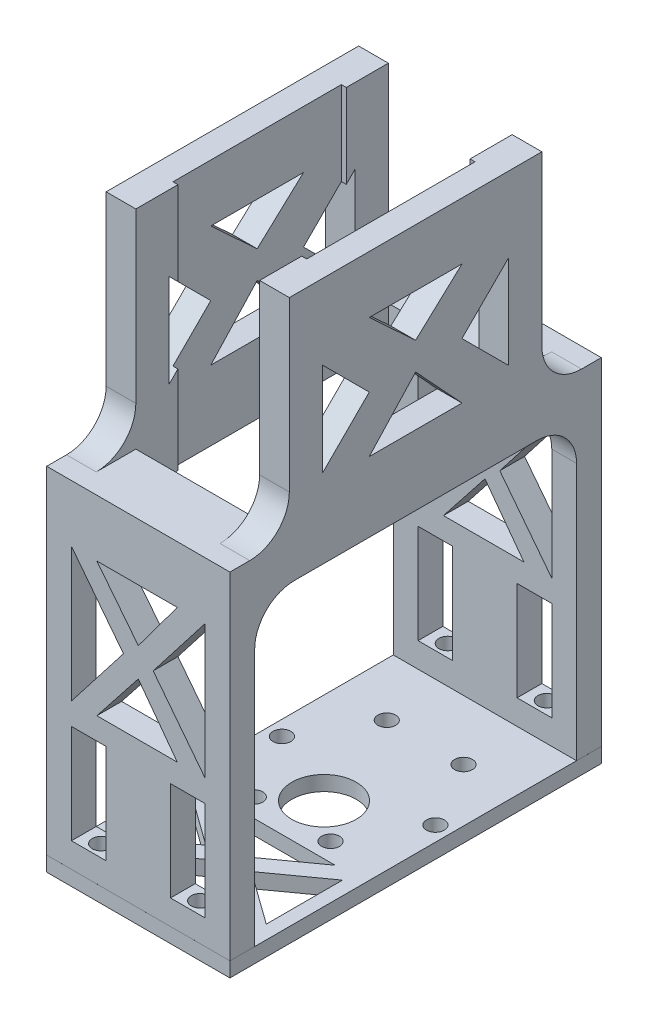
SolidWorks part; units mm, degrees
ref_plane "Front Plane" through (0, 0, 0) normal (0, 0, 1) x (1, 0, 0)
ref_plane "Top Plane" through (0, 0, 0) normal (0, 1, 0) x (1, 0, 0)
ref_plane "Right Plane" through (0, 0, 0) normal (1, 0, 0) x (0, 0, -1)
sketch "Sketch2" plane through (0, 0, 0) normal (0, 1, 0) x (1, 0, 0)
  line L1 (7.75, -13.4234) -> (15.5, 0) construction
  line L2 (15.5, 0) -> (7.75, 13.4234) construction
  line L3 (7.75, 13.4234) -> (-7.75, 13.4234) construction
  line L4 (-7.75, 13.4234) -> (-15.5, 0) construction
  line L5 (-15.5, 0) -> (-7.75, -13.4234) construction
  line L6 (-7.75, -13.4234) -> (7.75, -13.4234) construction
  circle A0 centre (0, 0) radius 13.4234 construction
  circle A1 centre (-15.5, 0) radius 1.8
  circle A2 centre (-7.75, 13.4234) radius 1.8
  circle A3 centre (7.75, 13.4234) radius 1.8
  circle A4 centre (15.5, 0) radius 1.8
  circle A5 centre (7.75, -13.4234) radius 1.8
  circle A6 centre (-7.75, -13.4234) radius 1.8
  circle A7 centre (0, 0) radius 18.5
  dimension "D2" = 3.6
  dimension "D3" = 37
  dimension "D1" = 31
extrude "Boss-Extrude1" add sketch "Sketch2" along normal blind 3
sketch "Sketch3" plane through (0, 3, 0) normal (0, 1, 0) x (1, 0, 0)
  line L0 (0, 0) -> (0, -7) construction
  circle A0 centre (0, -7) radius 6.5
  dimension "D2" = 13
  dimension "D1" = 7
extrude "Cut-Extrude1" cut sketch "Sketch3" against normal blind 3
sketch "Sketch4" plane through (0, 3, 0) normal (0, 1, 0) x (1, 0, 0)
  line L1 (-18.5, 30.5) -> (18.5, 30.5)
  line L4 (-18.5, -44.5) -> (18.5, -44.5)
  line L6 (-18.5, -44.5) -> (-18.5, 30.5)
  line L7 (18.5, 30.5) -> (18.5, -44.5)
  line L8 (0, -7) -> (2.9813, -7) construction
  circle A1 centre (0, 0) radius 18.5
  circle A2 centre (0, 0) radius 18.5
  point P7 (18.5, -7)
  circle M11 centre (0, 0) radius 18.5
  dimension "D2" = 75
  dimension "D1" = 0
extrude "Boss-Extrude2" add sketch "Sketch4" against normal up to surface (3 mm away) contours L7 L1 L6 M11 | L7 L6 L4 M11 region at (0, 3, -21.9811) region at (0, 3, 29.2305) up to face at (0, 0, 13.5)
sketch "Sketch5" plane through (0, 3, 0) normal (0, 1, 0) x (1, 0, 0)
  line L0 (18.5, 30.5) -> (18.5, -44.5) construction
  line L1 (-18.5, 30.5) -> (18.5, 30.5)
  line L2 (-18.5, 30.5) -> (-18.5, 25.5)
  line L3 (-18.5, 25.5) -> (18.5, 25.5)
  line L4 (18.5, 30.5) -> (18.5, 25.5)
  line L6 (-18.5, -44.5) -> (18.5, -44.5)
  line L7 (-18.5, -44.5) -> (-18.5, -39.5)
  line L8 (-18.5, -39.5) -> (18.5, -39.5)
  line L9 (18.5, -44.5) -> (18.5, -39.5)
  dimension "D1" = 5
extrude "Boss-Extrude3" add sketch "Sketch5" along normal blind 90
sketch "Sketch6" plane through (0, 93, 0) normal (0, 1, 0) x (1, 0, 0)
  line L0 (18.5, 25.5) -> (18.5, -39.5) construction
  line L1 (-18.5, 25.5) -> (18.5, 25.5)
  line L2 (-18.5, 25.5) -> (-18.5, 10)
  line L3 (-18.5, 10) -> (18.5, 10)
  line L4 (18.5, 25.5) -> (18.5, 10)
  line L6 (-18.5, -39.5) -> (18.5, -39.5)
  line L7 (-18.5, -39.5) -> (-18.5, -24)
  line L8 (-18.5, -24) -> (18.5, -24)
  line L9 (18.5, -39.5) -> (18.5, -24)
  dimension "D1" = 34
extrude "Boss-Extrude4" add sketch "Sketch6" against normal blind 5
sketch "Sketch7" plane through (0, 93, 0) normal (0, 1, 0) x (1, 0, 0)
  line L0 (18.5, 30.5) -> (-18.5, 30.5) construction
  line L1 (-18.5, 10) -> (-12.5, 10)
  line L2 (-18.5, 10) -> (-18.5, 30.5)
  line L3 (-18.5, 30.5) -> (-12.5, 30.5)
  line L4 (-12.5, 10) -> (-12.5, 30.5)
  line L5 (18.5, 10) -> (12.5, 10)
  line L6 (18.5, 10) -> (18.5, 30.5)
  line L7 (18.5, 30.5) -> (12.5, 30.5)
  line L8 (12.5, 10) -> (12.5, 30.5)
  line L9 (-18.5, -24) -> (-12.5, -24)
  line L10 (-18.5, -24) -> (-18.5, -44.5)
  line L11 (-18.5, -44.5) -> (-12.5, -44.5)
  line L12 (-12.5, -24) -> (-12.5, -44.5)
  line L13 (18.5, -24) -> (12.5, -24)
  line L14 (18.5, -24) -> (18.5, -44.5)
  line L15 (18.5, -44.5) -> (12.5, -44.5)
  line L16 (12.5, -24) -> (12.5, -44.5)
  dimension "D1" = 25
extrude "Boss-Extrude5" add sketch "Sketch7" along normal blind 20
sketch "Sketch8" plane through (0, 93, 0) normal (0, 1, 0) x (1, 0, 0)
  line L0 (-12.5, 10) -> (-12.5, 25.5)
  line L1 (-12.5, 10) -> (-12.5, 30.5) construction
  line L2 (-12.5, 25.5) -> (12.5, 25.5)
  line L3 (12.5, 30.5) -> (12.5, 10) construction
  line L4 (12.5, 25.5) -> (12.5, 10)
  line L5 (12.5, 10) -> (-12.5, 10)
  line L6 (-12.5, -24) -> (12.5, -24)
  line L7 (12.5, -24) -> (12.5, -39.5)
  line L8 (12.5, -24) -> (12.5, -44.5) construction
  line L9 (12.5, -39.5) -> (-12.5, -39.5)
  line L10 (-12.5, -44.5) -> (-12.5, -24) construction
  line L11 (-12.5, -39.5) -> (-12.5, -24)
  line L12 (-18.5, 25.5) -> (18.5, 25.5) construction
  line L13 (18.5, -39.5) -> (-18.5, -39.5) construction
extrude "Cut-Extrude2" cut sketch "Sketch8" against normal blind 10
sketch "Sketch9" plane through (0, 93, 0) normal (0, 1, 0) x (1, 0, 0)
  line L0 (12.5, 30.5) -> (12.5, 10) construction
  line L1 (-12.5, 30.5) -> (12.5, 30.5)
  line L2 (-12.5, 30.5) -> (-12.5, 25.5)
  line L3 (-12.5, 25.5) -> (12.5, 25.5)
  line L4 (12.5, 30.5) -> (12.5, 25.5)
  line L5 (-18.5, 25.5) -> (18.5, 25.5) construction
  line L7 (-12.5, -39.5) -> (12.5, -39.5)
  line L8 (-12.5, -39.5) -> (-12.5, -44.5)
  line L9 (-12.5, -44.5) -> (12.5, -44.5)
  line L10 (12.5, -39.5) -> (12.5, -44.5)
extrude "Boss-Extrude6" add sketch "Sketch9" along normal up to surface (20 mm away) up to face at (-15.5, 113, -20.25)
sketch "Sketch10" plane through (0, 0, 24) normal (0, 0, -1) x (-1, 0, 0)
  line L0 (12.5, 88) -> (18.5, 88) construction
  line L1 (18.5, 113) -> (13.5, 113)
  line L2 (18.5, 113) -> (18.5, 88)
  line L3 (18.5, 88) -> (13.5, 88)
  line L4 (13.5, 113) -> (13.5, 88)
  line L5 (-18.5, 88) -> (-12.5, 88) construction
  line L6 (-18.5, 113) -> (-13.5, 113)
  line L7 (-18.5, 113) -> (-18.5, 88)
  line L8 (-18.5, 88) -> (-13.5, 88)
  line L9 (-13.5, 113) -> (-13.5, 88)
  dimension "D1" = 5
extrude "Boss-Extrude7" add sketch "Sketch10" along normal up to next
sketch "Sketch11" plane through (0, 0, 44.5) normal (0, 0, 1) x (1, 0, 0)
  line L0 (-18.5, 113) -> (18.5, 113) construction
  line L1 (-12.5, 113) -> (12.5, 113)
  line L2 (-12.5, 113) -> (-12.5, 93)
  line L3 (-12.5, 93) -> (12.5, 93)
  line L4 (12.5, 113) -> (12.5, 93)
  line L7 (0, 93) -> (0, 113) construction
  line L8 (-18.5, 0) -> (-18.5, 113) construction
  line L9 (18.5, 0) -> (18.5, 113) construction
  line L10 (-12.5, 113) -> (-12.5, 88) construction
  dimension "D1" = 20
extrude "Cut-Extrude3" cut sketch "Sketch11" against normal through all
ref_plane "Plane1" through (12.5, 88, 39.5) normal (1, 0, 0) x (0, 0, -1)
sketch "Sketch13" plane through (18.5, 0, 0) normal (1, 0, 0) x (0, 0, -1)
  line L1 (-44.5, 113) -> (-32.5, 113)
  line L2 (-44.5, 113) -> (-44.5, 63)
  line L3 (-44.5, 63) -> (-32.5, 63)
  line L4 (-32.5, 113) -> (-32.5, 63)
  line L5 (30.5, 113) -> (18.5, 113)
  line L6 (30.5, 113) -> (30.5, 63)
  line L7 (30.5, 63) -> (18.5, 63)
  line L8 (18.5, 113) -> (18.5, 63)
  dimension "D1" = 12
  dimension "D2" = 50
extrude "Cut-Extrude5" cut sketch "Sketch13" against normal through all
sketch "Sketch14" plane through (0, 88, 0) normal (0, -1, 0) x (1, 0, 0)
  line L8 (18.5, -18.5) -> (18.5, 32.5)
  line L9 (18.5, 32.5) -> (12.5, 32.5)
  line L10 (12.5, 32.5) -> (12.5, 24)
  line L11 (12.5, 24) -> (13.5, 24)
  line L12 (13.5, 24) -> (13.5, -10)
  line L13 (13.5, -10) -> (12.5, -10)
  line L14 (12.5, -10) -> (12.5, -18.5)
  line L15 (12.5, -18.5) -> (18.5, -18.5)
  line L16 (18.5, -18.5) -> (18.5, 32.5)
  line L17 (18.5, 32.5) -> (12.5, 32.5)
  line L18 (12.5, 32.5) -> (12.5, 24)
  line L19 (12.5, 24) -> (13.5, 24)
  line L20 (13.5, 24) -> (13.5, -10)
  line L21 (13.5, -10) -> (12.5, -10)
  line L22 (12.5, -10) -> (12.5, -18.5)
  line L23 (12.5, -18.5) -> (18.5, -18.5)
  line L24 (-12.5, 32.5) -> (-18.5, 32.5)
  line L25 (-18.5, 32.5) -> (-18.5, -18.5)
  line L26 (-18.5, -18.5) -> (-12.5, -18.5)
  line L27 (-12.5, -18.5) -> (-12.5, -10)
  line L28 (-12.5, -10) -> (-13.5, -10)
  line L29 (-13.5, -10) -> (-13.5, 24)
  line L30 (-13.5, 24) -> (-12.5, 24)
  line L31 (-12.5, 24) -> (-12.5, 32.5)
  line L32 (-12.5, 32.5) -> (-18.5, 32.5)
  line L33 (-18.5, 32.5) -> (-18.5, -18.5)
  line L34 (-18.5, -18.5) -> (-12.5, -18.5)
  line L35 (-12.5, -18.5) -> (-12.5, -10)
  line L36 (-12.5, -10) -> (-13.5, -10)
  line L37 (-13.5, -10) -> (-13.5, 24)
  line L38 (-13.5, 24) -> (-12.5, 24)
  line L39 (-12.5, 24) -> (-12.5, 32.5)
  dimension "D1" = 0
  dimension "D2" = 0
extrude "Boss-Extrude8" add sketch "Sketch14" along normal up to surface (25 mm away) up to face at (0, 63, 42)
sketch "Sketch16" plane through (0, 0, 32.5) normal (0, 0, 1) x (1, 0, 0)
  line L0 (18.5, 63) -> (18.5, 113) construction
  line L1 (-18.5, 63) -> (18.5, 63)
  line L2 (-18.5, 63) -> (-18.5, 71)
  line L3 (-18.5, 71) -> (18.5, 71)
  line L4 (18.5, 63) -> (18.5, 71)
  line L5 (-18.5, 63) -> (-18.5, 113) construction
  dimension "D1" = 8
extrude "Boss-Extrude9" add sketch "Sketch16" along normal up to surface (12 mm away) up to face at (0, 31.5, 44.5)
sketch "Sketch17" plane through (0, 0, -18.5) normal (0, 0, -1) x (-1, 0, 0)
  line L0 (-18.5, 71) -> (18.5, 71) construction
  line L1 (-18.5, 71) -> (18.5, 71)
  line L2 (18.5, 63) -> (-18.5, 63) construction
  line L3 (18.5, 63) -> (-18.5, 63)
  line L4 (-18.5, 63) -> (-18.5, 71)
  line L5 (18.5, 63) -> (18.5, 71)
extrude "Boss-Extrude10" add sketch "Sketch17" along normal up to surface (12 mm away) up to face at (0, 31.5, -30.5)
fillet "Fillet1" radius 8 2 edges at (0, 63, -25.5) (0, 63, 39.5)
fillet "Fillet2" radius 8 4 edges at (15.5, 71, -18.5) (-15.5, 71, -18.5) (-15.5, 71, 32.5) (15.5, 71, 32.5)
sketch "Sketch18" plane through (0, 3, 0) normal (0, 1, 0) x (1, 0, 0)
  line L4 (18.5, -44.5) -> (18.5, 30.5)
  line L5 (-18.5, -44.5) -> (18.5, -44.5)
  line L6 (-18.5, 30.5) -> (-18.5, -44.5)
  line L7 (18.5, 30.5) -> (-18.5, 30.5)
  line L8 (18.5, -44.5) -> (18.5, 30.5)
  line L9 (-18.5, -44.5) -> (18.5, -44.5)
  line L10 (-18.5, 30.5) -> (-18.5, -44.5)
  line L11 (18.5, 30.5) -> (-18.5, 30.5)
  dimension "D1" = 0
extrude "Cut-Extrude6" cut sketch "Sketch18" along normal blind 0.001
sketch "Sketch19" plane through (0, 0, 0) normal (0, -1, 0) x (1, 0, 0)
  line L0 (-18.5, -30.5) -> (-18.5, -25.5) construction
  line L1 (-18.5, -30.5) -> (-18.5, -25.5) construction
  line L2 (-18.5, 39.5) -> (-18.5, 44.5) construction
  line L3 (-18.5, 39.5) -> (-18.5, 44.5) construction
  line L4 (18.5, 44.5) -> (18.5, 39.5) construction
  line L5 (18.5, 44.5) -> (18.5, 39.5) construction
  line L6 (18.5, -25.5) -> (18.5, -30.5) construction
  line L7 (18.5, -25.5) -> (18.5, -30.5) construction
  line L8 (-18.5, 42) -> (18.5, 42) construction
  line L9 (-18.5, -28) -> (18.5, -28) construction
  line L10 (0, 0) -> (0, -6.5767) construction
  circle A0 centre (-10, 42) radius 1.8
  circle A1 centre (10, 42) radius 1.8
  circle A2 centre (-10, -28) radius 1.8
  circle A3 centre (10, -28) radius 1.8
  dimension "D1" = 3.6
  dimension "D2" = 10
  dimension "D3" = 10
extrude "Cut-Extrude7" cut sketch "Sketch19" against normal blind 8
sketch "Sketch20" plane through (0, 8, 0) normal (0, -1, 0) x (1, 0, 0)
  line L0 (18.5, 44.5) -> (-18.5, 44.5) construction
  line L1 (-13.5, 44.5) -> (-6.5, 44.5)
  line L2 (-13.5, 44.5) -> (-13.5, 39.5)
  line L3 (-13.5, 39.5) -> (-6.5, 39.5)
  line L4 (-6.5, 44.5) -> (-6.5, 39.5)
  line L5 (-13.5, 44.5) -> (-6.5, 39.5) construction
  line L6 (-13.5, 39.5) -> (-6.5, 44.5) construction
  line L7 (6.5, 44.5) -> (13.5, 44.5)
  line L8 (6.5, 44.5) -> (6.5, 39.5)
  line L9 (6.5, 39.5) -> (13.5, 39.5)
  line L10 (13.5, 44.5) -> (13.5, 39.5)
  line L11 (6.5, 44.5) -> (13.5, 39.5) construction
  line L12 (6.5, 39.5) -> (13.5, 44.5) construction
  line L13 (0, 7) -> (3.3966, 7) construction
  line L14 (-13.5, -30.5) -> (-13.5, -25.5)
  line L15 (-13.5, -30.5) -> (-6.5, -30.5)
  line L16 (-6.5, -30.5) -> (-6.5, -25.5)
  line L17 (6.5, -25.5) -> (13.5, -25.5)
  line L18 (-13.5, -25.5) -> (-6.5, -25.5)
  line L19 (13.5, -30.5) -> (13.5, -25.5)
  line L20 (6.5, -30.5) -> (13.5, -30.5)
  line L21 (6.5, -30.5) -> (6.5, -25.5)
  point P0 (-10, 42)
  point P6 (10, 42)
  dimension "D1" = 7
extrude "Cut-Extrude8" cut sketch "Sketch20" against normal blind 20
sketch "Sketch21" plane through (-18.5, 0, 0) normal (-1, 0, 0) x (0, 0, 1)
  line L0 (-18.5, 113) -> (18.536, 78.964) construction
  line L4 (32.5, 113) -> (-0.1808, 77.4386) construction
  line L5 (-11.8064, 97.8512) -> (-11.8064, 78.964)
  line L7 (-11.8064, 78.964) -> (-2.3628, 88.4076)
  line L8 (-2.3628, 88.4076) -> (-11.8064, 97.8512)
  line L9 (7, 3) -> (7, 20.8388) construction
  line L10 (44.5, 3) -> (-30.5, 3) construction
  line L11 (25.8064, 78.964) -> (16.3628, 88.4076)
  line L12 (25.8064, 97.8512) -> (25.8064, 78.964)
  line L13 (16.3628, 88.4076) -> (25.8064, 97.8512)
  line L14 (-2.3628, 77.1233) -> (16.3628, 77.1233)
  line L15 (16.3628, 77.1233) -> (7, 87.2415)
  line L16 (7, 87.2415) -> (-2.3628, 77.1233)
  line L17 (-2.3628, 101.4479) -> (16.3628, 101.4479)
  line L18 (16.3628, 101.4479) -> (7, 92.7841)
  line L19 (7, 92.7841) -> (-2.3628, 101.4479)
extrude "Cut-Extrude9" cut sketch "Sketch21" against normal through all and the other way through all
sketch "Sketch22" plane through (0, 0, -30.5) normal (0, 0, -1) x (-1, 0, 0)
  line L0 (0, 71) -> (0, 24.1527) construction
  line L1 (18.5, 71) -> (-18.5, 71) construction
  line L2 (-13.5, 28) -> (-13.5, 59.5) construction
  line L3 (-13.5, 59.5) -> (-3, 45.9688)
  line L4 (-3, 45.9688) -> (-13.5, 32.4375)
  line L5 (-13.5, 32.4375) -> (-13.5, 59.5)
  line L6 (3, 45.9688) -> (13.5, 32.4375)
  line L7 (13.5, 59.5) -> (3, 45.9688)
  line L8 (13.5, 32.4375) -> (13.5, 59.5)
  line L9 (-7.8754, 32.4375) -> (8.3725, 32.4375)
  line L10 (8.3725, 32.4375) -> (0, 43.0574)
  line L11 (0, 43.0574) -> (-7.8754, 32.4375)
  line L12 (-3, 45.9688) -> (3, 45.9688) construction
  line L13 (8.3725, 59.5) -> (0, 48.8801)
  line L14 (-7.8754, 59.5) -> (8.3725, 59.5)
  line L15 (0, 48.8801) -> (-7.8754, 59.5)
  dimension "D1" = 3
extrude "Cut-Extrude10" cut sketch "Sketch22" against normal through all
sketch "Sketch23" plane through (0, 0, 0) normal (0, -1, 0) x (1, 0, 0)
  line L0 (-11.505, 36.2626) -> (12.4053, 36.2626)
  line L1 (12.4053, 36.2626) -> (0.4502, 27.6589)
  line L2 (0.4502, 27.6589) -> (-11.505, 36.2626)
  line L3 (0.4502, 25.7581) -> (-11.505, 17.1544)
  line L4 (-11.505, 17.1544) -> (12.4053, 17.1544)
  line L5 (12.4053, 17.1544) -> (0.4502, 25.7581)
  line L6 (-14.8462, 34.4051) -> (-14.8462, 19.0119)
  line L7 (-14.8462, 19.0119) -> (-4.1515, 26.7085)
  line L8 (-4.1515, 26.7085) -> (-14.8462, 34.4051)
  line L9 (0.4502, 27.6589) -> (0.4502, 25.7581) construction
  line L10 (15.7466, 19.0119) -> (5.0519, 26.7085)
  line L11 (15.7466, 34.4051) -> (15.7466, 19.0119)
  line L12 (5.0519, 26.7085) -> (15.7466, 34.4051)
extrude "Cut-Extrude11" cut sketch "Sketch23" against normal blind 15
